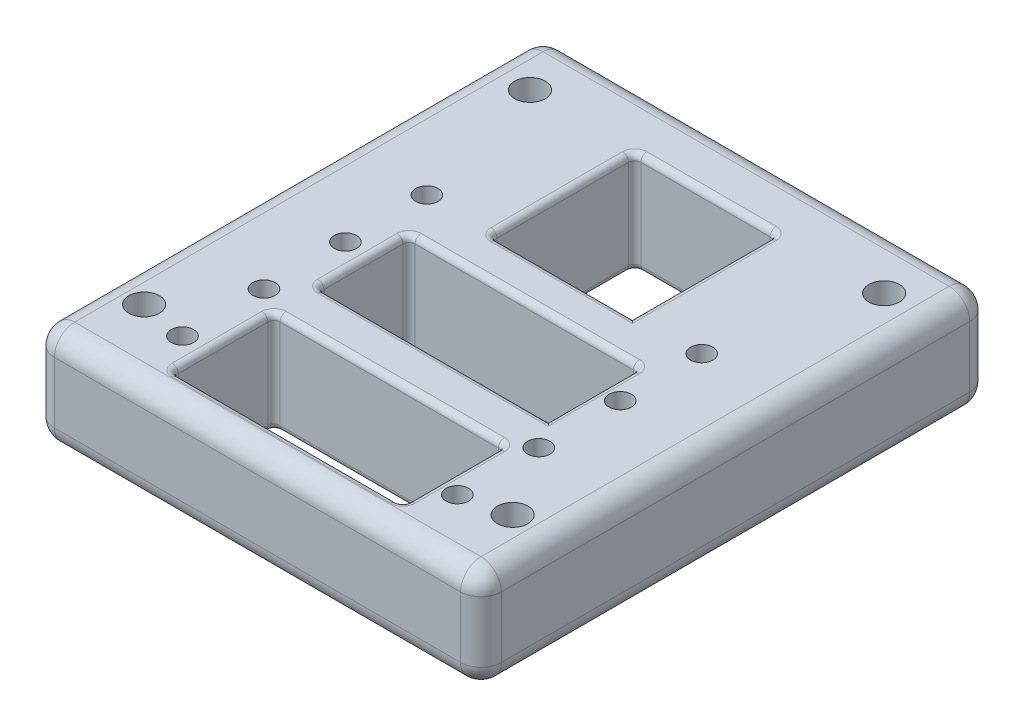
SolidWorks part; units mm, degrees
ref_plane "Front Plane" through (0, 0, 0) normal (0, 0, 1) x (1, 0, 0)
ref_plane "Top Plane" through (0, 0, 0) normal (0, 1, 0) x (1, 0, 0)
ref_plane "Right Plane" through (0, 0, 0) normal (1, 0, 0) x (0, 0, -1)
sketch "Sketch1" plane through (0, 0, 0) normal (0, 1, 0) x (1, 0, 0)
  line L1 (0, 0) -> (43.9, 0)
  line L2 (0, 0) -> (0, 50)
  line L3 (0, 50) -> (43.9, 50)
  line L4 (43.9, 0) -> (43.9, 50)
  dimension "D1" = 50
  dimension "D2" = 43.9
extrude "Boss-Extrude1" add sketch "Sketch1" along normal blind 10
sketch "Sketch2" plane through (0, 0, 0) normal (0, -1, 0) x (1, 0, 0)
  line L0 (0, -50) -> (0, 0) construction
  line L1 (15, -29.8751) -> (28.9, -29.8751)
  line L2 (15, -29.8751) -> (15, -44)
  line L3 (15, -44) -> (28.9, -44)
  line L4 (28.9, -29.8751) -> (28.9, -44)
  line L5 (43.9, -50) -> (0, -50) construction
  line L6 (43.9, 0) -> (43.9, -50) construction
  line L8 (10.8716, -16.998) -> (33.5171, -16.998)
  line L9 (10.8716, -16.998) -> (10.8716, -25.958)
  line L10 (10.8716, -25.958) -> (33.5171, -25.958)
  line L11 (33.5171, -16.998) -> (33.5171, -25.958)
  line L12 (10.8716, -2.6988) -> (33.5171, -2.6988)
  line L13 (10.8716, -2.6988) -> (10.8716, -12.7021)
  line L14 (10.8716, -12.7021) -> (33.5171, -12.7021)
  line L15 (33.5171, -2.6988) -> (33.5171, -12.7021)
  dimension "D1" = 15
  dimension "D2" = 6
  dimension "D3" = 15
extrude "Cut-Extrude1" cut sketch "Sketch2" against normal blind 10 contours L13 L12 L15 L14 | L9 L8 L11 L10 | L2 L1 L4 L3
sketch "Sketch6" plane through (0, 10, 0) normal (0, 1, 0) x (1, 0, 0)
  circle A0 centre (8.4727, 30.1106) radius 1.1
  circle A1 centre (8.4727, 22.1106) radius 1.1
  circle A2 centre (8.4727, 14.1106) radius 1.1
  circle A3 centre (8.4727, 6.1106) radius 1.1
  circle A4 centre (35.4727, 6.1106) radius 1.1
  circle A5 centre (35.4727, 14.1106) radius 1.1
  circle A6 centre (35.4727, 22.1106) radius 1.1
  circle A7 centre (35.4727, 30.1106) radius 1.1
extrude "Cut-Extrude2" cut sketch "Sketch6" against normal blind 10
sketch "Sketch7" plane through (0, 0, 0) normal (0, -1, 0) x (1, 0, 0)
  line L0 (4.6053, -39.1106) -> (4.6053, -44.1106)
  line L1 (21.95, -44) -> (21.9374, -48.4603) construction
  line L2 (15, -44) -> (28.9, -44) construction
  line L3 (1.8053, -48.4603) -> (42.0694, -48.4603) construction
  line L4 (21.9053, 7.3894) -> (21.9374, 13.0772)
  line L9 (13.7553, 7.3894) -> (30.0553, 7.3894) construction
  line L10 (42.0694, 13.0772) -> (1.8053, 13.0772) construction
  line L11 (7.4053, -41.7606) -> (7.4053, 1.0394) construction
  line L12 (36.4053, 1.0394) -> (36.4053, -41.7606) construction
  circle A1 centre (4.6053, -44.1106) radius 1.5
  circle A2 centre (39.2937, -44.2088) radius 1.5
  circle A3 centre (39.9053, -7.1106) radius 1.5
  circle A4 centre (39.2053, -17.1106) radius 1.025 construction
  circle A5 centre (3.9053, -6.9088) radius 1.5
  point P23 (3.9053, -6.9088)
  point P24 (0, 0)
  dimension "D1" = 5
  dimension "D2" = 3
  dimension "D4" = 3
  dimension "D6" = 3.5
  dimension "D3" = 10
  dimension "D7" = 3.5
extrude "Cut-Extrude3" cut sketch "Sketch7" against normal blind 30 and the other way blind 30 contours A1 | A2 | A5 | A3 region at (3.5747, 0, -45.1412) region at (39.2937, 0, -44.2088)
fillet "Fillet1" radius 2 12 edges at (21.95, 10, -50) (21.95, 0, -50) (43.9, 10, -25) (43.9, 5, -50) (43.9, 0, -25) (21.95, 10, 0) (43.9, 5, 0) (21.95, 0, 0) (0, 5, -50) (0, 10, -25) (0, 5, 0) (0, 0, -25)
fillet "Fillet2" radius 0.6 34 edges at (28.9, 10, -36.9375) (28.9, 0, -36.9375) (21.95, 10, -29.8751) (21.95, 0, -29.8751) (33.5171, 10, -21.478) (33.5171, 0, -21.478) (22.1943, 10, -16.998) (22.1943, 0, -16.998) (33.5171, 10, -7.7005) (33.5171, 0, -7.7005) (21.95, 10, -44) (28.9, 5, -44) (21.95, 0, -44) (15, 5, -29.8751) (15, 10, -36.9375) (15, 5, -44) (15, 0, -36.9375) (22.1943, 10, -25.958) (33.5171, 5, -25.958) (22.1943, 0, -25.958) (10.8716, 5, -16.998) (10.8716, 10, -21.478) (10.8716, 5, -25.958) (10.8716, 0, -21.478) (22.1943, 10, -12.7021) (33.5171, 5, -12.7021) (22.1943, 0, -12.7021) (10.8716, 10, -7.7005) (10.8716, 5, -12.7021) (10.8716, 0, -7.7005) (33.5171, 5, -2.6988) (22.1943, 10, -2.6988) (10.8716, 5, -2.6988) (22.1943, 0, -2.6988)
